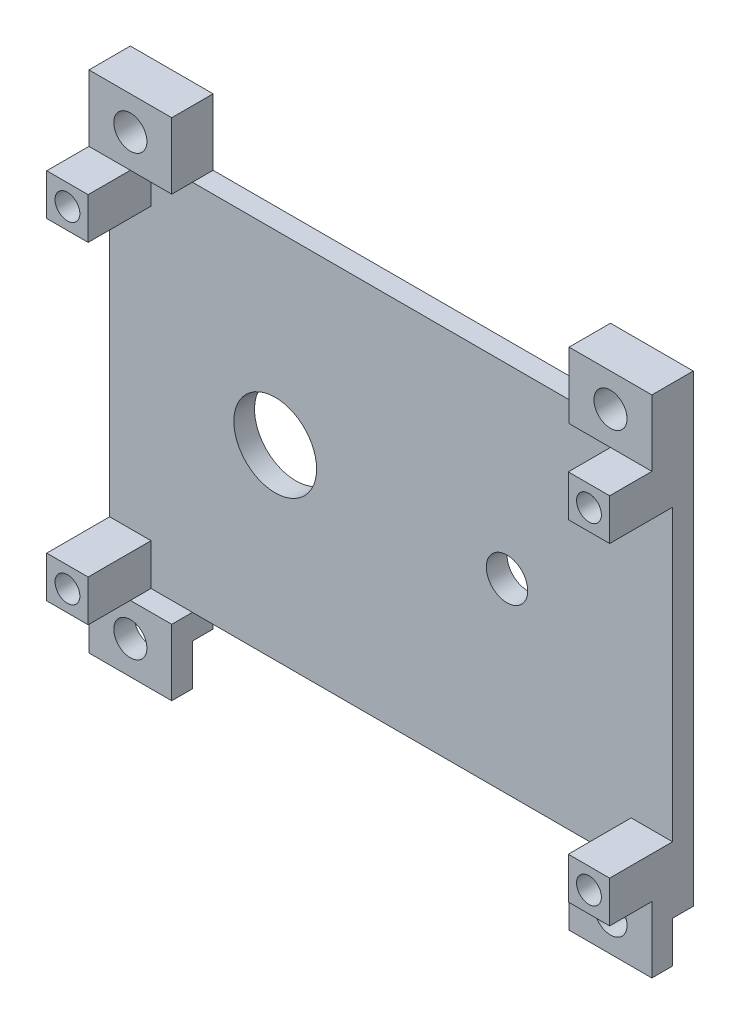
SolidWorks part; units mm, degrees
ref_plane "Přední rovina" through (0, 0, 0) normal (0, 0, 1) x (1, 0, 0)
ref_plane "Horní rovina" through (0, 0, 0) normal (0, 1, 0) x (1, 0, 0)
ref_plane "Pravá rovina" through (0, 0, 0) normal (1, 0, 0) x (0, 0, -1)
sketch "Skica1" plane through (0, 0, 0) normal (0, 0, 1) x (1, 0, 0)
  line L1 (-34, 22.5) -> (34, 22.5)
  line L2 (-34, 22.5) -> (-34, -22.5)
  line L3 (-34, -22.5) -> (34, -22.5)
  line L4 (34, 22.5) -> (34, -22.5)
  line L5 (-34, 22.5) -> (34, -22.5) construction
  line L6 (-34, -22.5) -> (34, 22.5) construction
  circle A0 centre (-14, 0) radius 5
  circle A1 centre (14, 0) radius 2.5
  point P0 (0, 0)
  point P8 (-34, 0)
  dimension "D2" = 10
  dimension "D4" = 5
  dimension "D1" = 45
  dimension "D3" = 20
  dimension "D5" = 28
  dimension "D6" = 68
extrude "Přidat vysunutím1" add sketch "Skica1" along normal blind 2.5
sketch "Skica2" plane through (0, 0, 2.5) normal (0, 0, 1) x (1, 0, 0)
  line L1 (-34, 22.5) -> (-29, 22.5)
  line L2 (-34, 22.5) -> (-34, 17.5)
  line L3 (-34, 17.5) -> (-29, 17.5)
  line L4 (-29, 22.5) -> (-29, 17.5)
  line L5 (34, 22.5) -> (29, 22.5)
  line L6 (34, 22.5) -> (34, 17.5)
  line L7 (34, 17.5) -> (29, 17.5)
  line L8 (29, 22.5) -> (29, 17.5)
  line L9 (34, -22.5) -> (29, -22.5)
  line L10 (34, -22.5) -> (34, -17.5)
  line L11 (34, -17.5) -> (29, -17.5)
  line L12 (29, -22.5) -> (29, -17.5)
  line L13 (-34, -22.5) -> (-29, -22.5)
  line L14 (-34, -22.5) -> (-34, -17.5)
  line L15 (-34, -17.5) -> (-29, -17.5)
  line L16 (-29, -22.5) -> (-29, -17.5)
  dimension "D1" = 5
  dimension "D3" = 5
  dimension "D5" = 5
  dimension "D8" = 5
extrude "Přidat vysunutím2" add sketch "Skica2" along normal blind 7.6
sketch "Skica3" plane through (0, 0, 10.1) normal (0, 0, 1) x (1, 0, 0)
  line L0 (-34, 22.5) -> (-29, 17.5) construction
  line L1 (-34, 17.5) -> (-29, 22.5) construction
  circle A0 centre (-31.5, 20) radius 1.5
  dimension "D1" = 3
extrude "Odebrat vysunutím1" cut sketch "Skica3" against normal blind 10.1
sketch "Skica8" plane through (0, 0, 10.1) normal (0, 0, 1) x (1, 0, 0)
  line L0 (29, 22.5) -> (34, 17.5) construction
  line L1 (29, 17.5) -> (34, 22.5) construction
  circle A0 centre (31.5, 20) radius 1.5
  dimension "D1" = 3
extrude "Odebrat vysunutím2" cut sketch "Skica8" against normal blind 10.1
sketch "Skica9" plane through (0, 0, 10.1) normal (0, 0, 1) x (1, 0, 0)
  line L0 (29, -17.5) -> (34, -22.5) construction
  line L1 (29, -22.5) -> (34, -17.5) construction
  circle A0 centre (31.5, -20) radius 1.5
  dimension "D1" = 3
extrude "Odebrat vysunutím3" cut sketch "Skica9" against normal blind 10.1
sketch "Skica10" plane through (0, 0, 10.1) normal (0, 0, 1) x (1, 0, 0)
  line L0 (-34, -17.5) -> (-29, -22.5) construction
  line L1 (-34, -22.5) -> (-29, -17.5) construction
  circle A0 centre (-31.5, -20) radius 1.5
  dimension "D1" = 3
extrude "Odebrat vysunutím4" cut sketch "Skica10" against normal blind 10.1
sketch "Skica11" plane through (0, 22.5, 0) normal (0, 1, 0) x (1, 0, 0)
  line L0 (29, -2.5) -> (-29, -2.5) construction
  line L1 (-34, 0) -> (-24, 0)
  line L2 (-34, 0) -> (-34, -2.5)
  line L3 (-34, -2.5) -> (-24, -2.5)
  line L4 (-24, 0) -> (-24, -2.5)
  line L6 (34, 0) -> (24, 0)
  line L7 (34, 0) -> (34, -2.5)
  line L8 (34, -2.5) -> (24, -2.5)
  line L9 (24, 0) -> (24, -2.5)
  dimension "D1" = 10
  dimension "D2" = 10
extrude "Přidat vysunutím3" add sketch "Skica11" along normal blind 8 and the other way blind 48
sketch "Skica12" plane through (0, 0, 2.5) normal (0, 0, 1) x (1, 0, 0)
  line L0 (-24, 22.5) -> (-24, 30.5) construction
  line L1 (-34, 30.5) -> (-24, 30.5) construction
  line L2 (0, -32.5458) -> (0, 31.9125) construction
  line L3 (-43.2311, 0) -> (46.4533, 0) construction
  circle A0 centre (-29, 26.5) radius 2
  circle A1 centre (29, 26.5) radius 2
  circle A2 centre (29, -26.5) radius 2
  circle A3 centre (-29, -26.5) radius 2
  dimension "D1" = 4
  dimension "D2" = 5
  dimension "D3" = 4
extrude "Odebrat vysunutím5" cut sketch "Skica12" against normal blind 8
sketch "Skica13" plane through (0, 0, 2.5) normal (0, 0, 1) x (1, 0, 0)
  line L0 (0, -32.5458) -> (0, 31.9125) construction
  line L1 (-34, 30.5) -> (-24, 30.5)
  line L2 (-34, 30.5) -> (-34, 22.5)
  line L3 (-34, 22.5) -> (-24, 22.5)
  line L4 (-24, 30.5) -> (-24, 22.5)
  line L5 (-43.2311, 0) -> (46.4533, 0) construction
  line L6 (34, 22.5) -> (24, 22.5)
  line L7 (24, 30.5) -> (24, 22.5)
  line L8 (34, 30.5) -> (24, 30.5)
  line L9 (34, 30.5) -> (34, 22.5)
  line L10 (34, -30.5) -> (34, -22.5)
  line L11 (34, -30.5) -> (24, -30.5)
  line L12 (24, -30.5) -> (24, -22.5)
  line L13 (34, -22.5) -> (24, -22.5)
  line L14 (-34, -22.5) -> (-24, -22.5)
  line L15 (-24, -30.5) -> (-24, -22.5)
  line L16 (-34, -30.5) -> (-24, -30.5)
  line L17 (-34, -30.5) -> (-34, -22.5)
  circle A0 centre (-29, 26.5) radius 2
  circle A1 centre (-29, 26.5) radius 2 construction
  circle A2 centre (29, 26.5) radius 2
  circle A3 centre (29, -26.5) radius 2
  circle A4 centre (-29, -26.5) radius 2
extrude "Přidat vysunutím4" add sketch "Skica13" along normal blind 2.5
